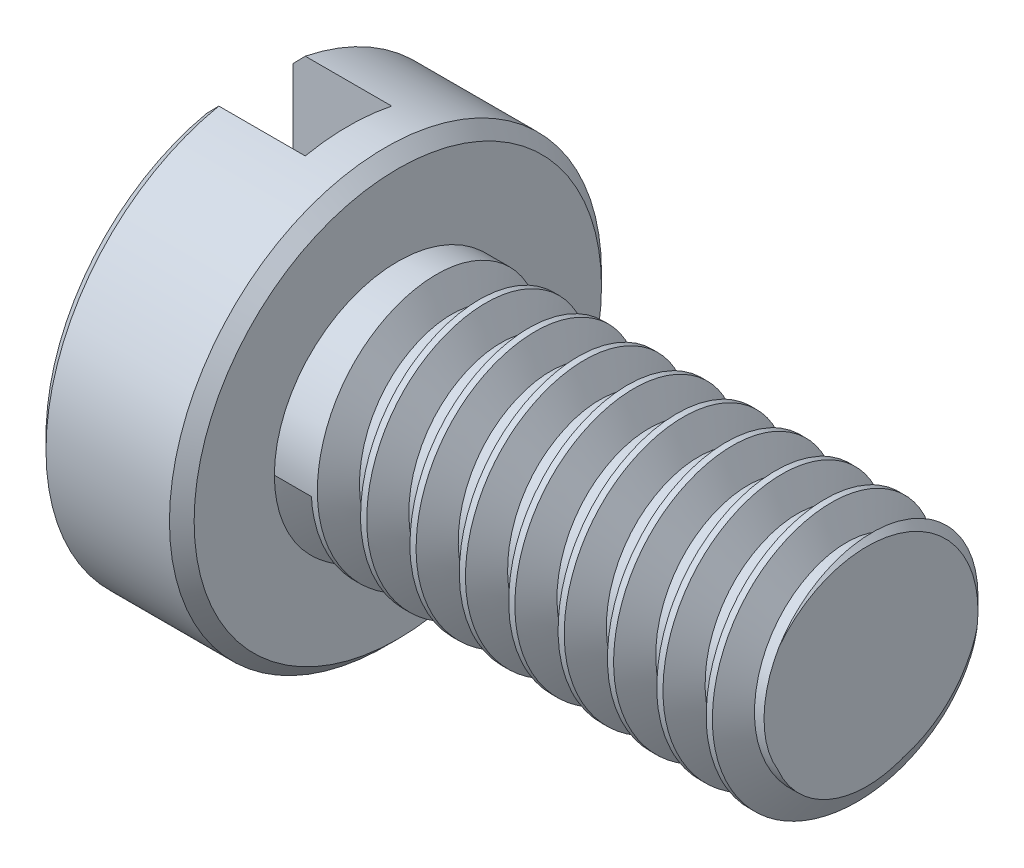
SolidWorks part; units mm, degrees
material "Латунь"
ref_plane "Front Plane" through (0, 0, 0) normal (0, 0, 1) x (1, 0, 0)
ref_plane "Top Plane" through (0, 0, 0) normal (0, 1, 0) x (1, 0, 0)
ref_plane "Right Plane" through (0, 0, 0) normal (1, 0, 0) x (0, 0, -1)
sketch "Эскиз1" plane through (0, 0, 0) normal (0, 0, 1) x (1, 0, 0)
  line L0 (0, 0) -> (4.8145, 0) construction
  line L1 (0, 0) -> (0, -1.75)
  line L2 (0, -1.75) -> (1.2, -1.75)
  line L3 (1.2, -1.75) -> (1.2, -1)
  line L4 (1.2, -1) -> (5, -1)
  line L5 (5, -1) -> (5, 0)
  line L6 (5, 0) -> (0, 0)
  dimension "D1" = 3.5
  dimension "D2" = 5
  dimension "D3" = 1.2
  dimension "D4" = 1
revolve "Повернуть1" add sketch "Эскиз1" angle 360 about L0
chamfer "Фаска1" distance 0.1 angle 45 3 edges at (5, 0, 1) (1.2, 0, 1.75) (0, 0, 1.75)
sketch "Эскиз2" plane through (0, 0, 0) normal (-1, 0, 0) x (0, 0, 1)
  line L1 (-0.35, 1.75) -> (0.35, 1.75)
  line L2 (-0.35, 1.75) -> (-0.35, -1.75)
  line L3 (-0.35, -1.75) -> (0.35, -1.75)
  line L4 (0.35, 1.75) -> (0.35, -1.75)
  line L5 (-0.35, 1.75) -> (0.35, -1.75) construction
  line L6 (-0.35, -1.75) -> (0.35, 1.75) construction
  circle A0 centre (0, 0) radius 1.75 construction
  point P0 (0, 0)
  dimension "D1" = 0.7
extrude "Вырез-Вытянуть1" cut sketch "Эскиз2" against normal blind 0.8
thread "Резьба1" pitch 0.4 method cut profile "Профиль резьбы1" start angle 0, offset 1, length 4.4, pitch 0.4, diameter 2
ref_plane "Плоскость1" through (5.9, 0, 1) normal (0, -1, 0) x (0, 0, 1)
sketch "Профиль резьбы1" plane through (5.9, 0, 1) normal (0, -1, 0) x (0, 0, 1)
  line L0 (0, 0) -> (0, 0.4) construction
  line L11 (0, 0) -> (0, 0.35)
  line L12 (0, 0.35) -> (-0.2165, 0.225)
  line L13 (-0.2165, 0.225) -> (-0.2165, 0.125)
  line L15 (-0.2165, 0.125) -> (0, 0)
  line L17 (-0.2165, 0.175) -> (0, 0.175) construction
  point P2 (0, 0)
  dimension "Pitch" = 0.4
  dimension "Profile_Angle" = 60
  dimension "Profile_Land" = 0.1
  dimension "Profile_Height" = 0.2165
